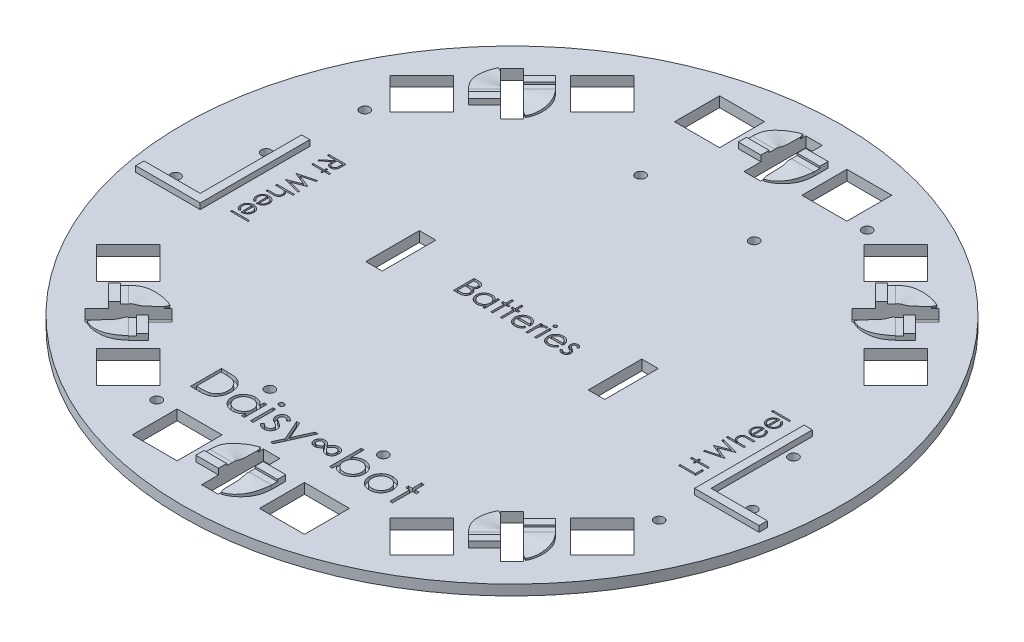
SolidWorks part; units mm, degrees
ref_plane "Front" through (0, 0, 0) normal (0, 0, 1) x (1, 0, 0)
ref_plane "Top" through (0, 0, 0) normal (0, 1, 0) x (1, 0, 0)
ref_plane "Right" through (0, 0, 0) normal (1, 0, 0) x (0, 0, -1)
sketch "Sketch1" plane through (0, 0, 0) normal (0, 1, 0) x (1, 0, 0)
  circle A0 centre (0, 0) radius 101.6
  dimension "D1" = 203.2
extrude "Boss-Extrude1" add sketch "Sketch1" along normal blind 3.175 contours A0
sketch "Sketch2" plane through (0, 3.175, 0) normal (0, 1, 0) x (1, 0, 0)
  line L1 (-2.54, -93.1333) -> (2.54, -93.1333)
  line L2 (-2.54, -93.1333) -> (-2.54, -74.0833)
  line L3 (-2.54, -74.0833) -> (2.54, -74.0833)
  line L4 (2.54, -93.1333) -> (2.54, -74.0833)
  circle A0 centre (0, 0) radius 101.6 construction
  point P4 (0, -74.0833)
  dimension "D1" = 5.08
  dimension "D2" = 19.05
  dimension "D3" = 93.1333
extrude "Cut-Extrude1" cut sketch "Sketch2" against normal up to next and the other way through all contours L1 L4 L3 L2
sketch "Sketch4" plane through (0, 3.175, 0) normal (0, 1, 0) x (1, 0, 0)
  line L0 (0, -83.6083) -> (-2.9434, -74.5495) construction
  line L1 (-2.9434, -74.5495) -> (0, -83.6083) construction
  line L2 (0, -83.6083) -> (-5.5987, -75.9025) construction
  line L3 (0, -83.6083) -> (-7.7059, -78.0097) construction
  line L4 (0, -83.6083) -> (-9.0588, -80.665) construction
  line L5 (0, -83.6083) -> (-9.525, -83.6083) construction
  line L9 (2.54, -74.0833) -> (-2.54, -74.0833) construction
  line L10 (2.54, -74.0833) -> (2.54, -93.1333) construction
  line L11 (-2.54, -74.0833) -> (-2.54, -93.1333) construction
  line L12 (2.54, -93.1333) -> (-2.54, -93.1333) construction
  circle A0 centre (0, -83.6083) radius 9.525 construction
  point P16 (0, -74.0833)
  point P19 (2.54, -83.6083)
  dimension "D1" = 18
  dimension "D2" = 18
  dimension "D3" = 18
  dimension "D4" = 18
  dimension "D5" = 18
ref_plane "Plane1" through (-24.5719, 0, 7.9839) normal (0.9511, 0, -0.309) x (-0.309, 0, -0.9511)
ref_plane "Plane2" through (-39.7581, 0, 28.886) normal (0.809, 0, -0.5878) x (-0.5878, 0, -0.809)
ref_plane "Plane3" through (-39.7581, 0, 54.7224) normal (0.5878, 0, -0.809) x (-0.809, 0, -0.5878)
ref_plane "Plane4" through (-24.5719, 0, 75.6245) normal (0.309, 0, -0.9511) x (-0.9511, 0, -0.309)
ref_plane "Plane5" through (0, 0, 83.6083) normal (0, 0, -1) x (-1, 0, 0)
sketch "Sketch5" plane through (-24.5719, 0, 7.9839) normal (0.9511, 0, -0.309) x (-0.309, 0, -0.9511)
  line L0 (-69.6725, 3.175) -> (-87.7902, 3.175) construction
  line L1 (-71.2966, 3.175) -> (-69.9913, 3.175)
  line L2 (-71.2966, 3.175) -> (-71.2966, 3.683)
  line L3 (-71.2966, 3.683) -> (-69.9913, 3.683)
  line L4 (-69.9913, 3.175) -> (-69.9913, 3.683)
  dimension "D2" = 0.508
sketch "Sketch6" plane through (-39.7581, 0, 28.886) normal (0.809, 0, -0.5878) x (-0.5878, 0, -0.809)
  line L0 (-58.4417, 3.175) -> (-73.8535, 3.175) construction
  line L1 (-63.3193, 3.175) -> (-58.1156, 3.175)
  line L2 (-63.3193, 3.175) -> (-63.3193, 3.775)
  line L3 (-63.3193, 3.775) -> (-58.1156, 3.775)
  line L4 (-58.1156, 3.175) -> (-58.1156, 3.775)
  dimension "D2" = 0.6
sketch "Sketch7" plane through (-39.7581, 0, 54.7224) normal (0.5878, 0, -0.809) x (-0.809, 0, -0.5878)
  line L0 (-41.4902, 3.175) -> (-52.6875, 3.175) construction
  line L1 (-46.0041, 3.175) -> (-39.6188, 3.175)
  line L2 (-46.0041, 3.175) -> (-46.0041, 4.075)
  line L3 (-46.0041, 4.075) -> (-39.6188, 4.075)
  line L4 (-39.6188, 3.175) -> (-39.6188, 4.075)
  dimension "D2" = 0.9
sketch "Sketch10" plane through (-24.5719, 0, 75.6245) normal (0.309, 0, -0.9511) x (-0.9511, 0, -0.309)
  line L0 (-25.8364, 3.175) -> (-16.7776, 3.175) construction
  line L1 (-23.1657, 3.175) -> (-16.3114, 3.175)
  line L2 (-23.1657, 3.175) -> (-23.1657, 4.375)
  line L3 (-23.1657, 4.375) -> (-16.3114, 4.375)
  line L4 (-16.3114, 3.175) -> (-16.3114, 4.375)
  dimension "D3" = 1.2
sketch "Sketch11" plane through (0, 0, 83.6083) normal (0, 0, -1) x (-1, 0, 0)
  line L0 (0, 3.175) -> (9.525, 3.175) construction
  line L1 (2.54, 3.175) -> (9.525, 3.175)
  line L2 (2.54, 3.175) -> (2.54, 4.375)
  line L3 (2.54, 4.375) -> (9.525, 4.375)
  line L4 (9.525, 3.175) -> (9.525, 4.375)
  dimension "D3" = 1.2
loft "Loft1" add profiles "Sketch5", "Sketch6", "Sketch7", "Sketch10", "Sketch11" connector at (-2.54, 3.683, 75.791) connector at (-2.54, 3.775, 80.1123) connector at (-2.54, 4.075, 81.7629) connector at (-2.54, 4.375, 82.783) connector at (-2.54, 4.375, 83.6083)
sketch "Sketch13" plane through (-104.9799, 0, 83.6083) normal (0, 0, -1) x (-1, 0, 0)
  line L6 (-95.4549, 3.175) -> (-102.4399, 3.175)
  line L7 (-95.4549, 3.175) -> (-95.4549, 4.375)
  line L8 (-95.4549, 4.375) -> (-102.4399, 4.375)
  line L9 (-102.4399, 3.175) -> (-102.4399, 4.375)
extrude "Boss-Extrude4" add sketch "Sketch13" against normal blind 1.7907
sketch "Sketch25" plane through (0, 0, 85.399) normal (0, 0, 1) x (1, 0, 0)
  line L0 (-9.525, 4.375) -> (-2.54, 4.375) construction
  line L1 (-9.525, 3.175) -> (-2.54, 3.175)
  line L2 (-9.525, 3.175) -> (-9.525, 4.975)
  line L3 (-9.525, 4.975) -> (-2.54, 4.975)
  line L4 (-2.54, 3.175) -> (-2.54, 4.975)
  dimension "D1" = 0.6
extrude "Boss-Extrude5" add sketch "Sketch25" along normal blind 2.54
sketch "Sketch14" plane through (-2.54, 0, 0) normal (1, 0, 0) x (0, 0, -1)
  line L0 (-83.6083, 3.175) -> (-83.6083, 0) construction
  line L1 (-74.0833, 0) -> (-93.1333, 0) construction
ref_plane "Plane6" through (0, 0, 0) normal (1, 0, 0) x (0, 0, -1)
sketch "Sketch15" plane through (0, 0, 0) normal (1, 0, 0) x (0, 0, -1)
  line L0 (-83.6083, 0) -> (-83.6083, 3.175) construction
pattern_circular "CirPattern1" count 2 over 360 about axis through (0, 0, 83.6083) along (0, 1, 0) of "Loft1", "Boss-Extrude5", "Boss-Extrude4" reverse direction yes
ref_axis "Axis1" through (0, 50, 0) along (0, -1, 0)
pattern_circular "CirPattern5" count 8 over 360 about axis through (0, 50, 0) along (0, -1, 0) skipping 2, 6 of "CirPattern1", "Cut-Extrude1"
sketch "Sketch18" plane through (0, 3.175, 0) normal (0, 1, 0) x (1, 0, 0)
  line L4 (0, -101.6) -> (0, 101.6) construction
  line L5 (0, -1.7463) -> (0, 1.7463) construction
  line L6 (-101.6, 0) -> (101.6, 0) construction
  circle A8 centre (0, 0) radius 101.6 construction
sketch "Sketch19" plane through (0, 3.175, 0) normal (0, 1, 0) x (1, 0, 0)
  line L0 (-32.0765, -77.4396) -> (0, 0) construction
  line L1 (0, -101.6) -> (0, 101.6) construction
  circle A1 centre (-32.0765, -77.4396) radius 1.5
  dimension "D1" = 83.82
  dimension "D4" = 3
  dimension "D5" = 22.5
extrude "Cut-Extrude2" cut sketch "Sketch19" against normal through all
pattern_circular "CirPattern7" count 4 over 360 about axis through (0, 50, 0) along (0, -1, 0) of "Cut-Extrude2"
sketch "Sketch23" plane through (0, 3.175, 0) normal (0, 1, 0) x (1, 0, 0)
  line L9 (-2.54, -87.939) -> (-2.54, -93.1333) construction
  line L10 (-26.5557, -76.6805) -> (-12.7, -76.6805)
  line L11 (-26.5557, -76.6805) -> (-26.5557, -90.5362)
  line L16 (-26.5557, -90.5362) -> (-12.7, -90.5362)
  line L17 (-12.7, -76.6805) -> (-12.7, -90.5362)
  line L19 (2.54, -74.0833) -> (2.54, -79.2776) construction
  line L20 (0, -50) -> (0, 50) construction
  line L21 (12.7, -76.6805) -> (12.7, -90.5362)
  line L22 (26.5557, -90.5362) -> (12.7, -90.5362)
  line L23 (26.5557, -76.6805) -> (26.5557, -90.5362)
  line L24 (26.5557, -76.6805) -> (12.7, -76.6805)
  point P8 (-2.54, -90.5362)
  point P9 (2.54, -76.6805)
  dimension "D2" = 10.16
extrude "Cut-Extrude6" cut sketch "Sketch23" against normal through all
pattern_circular "CirPattern8" count 8 over 360 about axis through (0, 50, 0) along (0, -1, 0) skipping 2, 6 of "Cut-Extrude6"
sketch "Sketch16" plane through (0, 3.175, 0) normal (0, 1, 0) x (1, 0, 0)
  line L0 (2.54, -74.0833) -> (-2.54, -74.0833) construction
  line L1 (-16.4163, -2.4279) -> (16.4163, -2.4279) construction
  line L2 (0, -101.6) -> (0, 101.6) construction
  line L3 (-71.12, 15.3104) -> (-71.12, -15.3104) construction
  line L4 (-101.6, 0) -> (101.6, 0) construction
  line L5 (71.12, 15.3104) -> (71.12, -15.3104) construction
  line L6 (-31.75, -68.58) -> (31.75, -68.58) construction
  circle A1 centre (0, 0) radius 101.6 construction
  text T0 "Daisy∞bot\r\n" font "Century Gothic" height in points 36
  text T1 "Batteries"
  text T2 "Rt Wheel\r\n" font "Century Gothic" height in points 20
  text T3 "Lt Wheel" font "Century Gothic" height in points 20
  point P4 (-71.12, 0)
  point P7 (0, -68.58)
  point P10 (0, -2.4279)
  point P15 (71.12, 0)
  dimension "D1" = 32.8326
  dimension "D2" = 30.6207
  dimension "D3" = 63.5
  dimension "D4" = 71.12
  dimension "D5" = 71.12
  dimension "D6" = 68.58
extrude "Cut-Extrude4" cut sketch "Sketch16" against normal blind 1.27
sketch "Sketch26" plane through (0, 3.175, 0) normal (0, 1, 0) x (1, 0, 0)
  line L0 (-101.6, 0) -> (101.6, 0) construction
  line L1 (-36.83, 8.255) -> (-31.75, 8.255)
  line L2 (-36.83, 8.255) -> (-36.83, -8.255)
  line L3 (-36.83, -8.255) -> (-31.75, -8.255)
  line L4 (-31.75, 8.255) -> (-31.75, -8.255)
  line L5 (0, -101.6) -> (0, 101.6) construction
  point P4 (-36.83, 0)
  dimension "D1" = 16.51
  dimension "D2" = 5.08
  dimension "D3" = 31.75
extrude "Cut-Extrude7" cut sketch "Sketch26" against normal through all
mirror "Mirror1" about plane through (0, 0, 0) normal (1, 0, 0) of "Cut-Extrude7"
sketch "Sketch27" plane through (0, 0, 0) normal (0, -1, 0) x (1, 0, 0)
  line L0 (0, 101.6) -> (0, -101.6) construction
  line L1 (-101.6, 0) -> (101.6, 0) construction
  circle A0 centre (-17.5, -57.15) radius 1.5
  circle A1 centre (-77.4396, -32.0765) radius 1.5 construction
  dimension "D1" = 17.5
  dimension "D2" = 57.15
extrude "Cut-Extrude8" cut sketch "Sketch27" against normal through all both and the other way through all
mirror "Mirror2" about plane through (0, 0, 0) normal (0, 0, 1) of "Cut-Extrude8"
mirror "Mirror3" about plane through (0, 0, 0) normal (1, 0, 0) of "Mirror2"
sketch "Sketch28" plane through (0, 0, 0) normal (0, -1, 0) x (1, 0, 0)
  line L0 (-21.8435, -50.8) -> (21.8435, -50.8) construction
  line L1 (0, 101.6) -> (0, -101.6) construction
  line L2 (-101.6, 0) -> (101.6, 0) construction
  line L3 (-19.568, 50.8) -> (19.568, 50.8) construction
  text T0 "Bk Caster"
  text T1 "Ft Caster"
  point P3 (0, 50.8)
  point P4 (0, -50.8)
  dimension "D1" = 50.8
  dimension "D2" = 50.8
extrude "Cut-Extrude9" cut sketch "Sketch28" against normal blind 1.27
ref_plane "Plane7" through (101.6, 3.175, 0) normal (1, 0, 0) x (0, 0, -1)
sketch "Sketch33" plane through (0, 3.175, 0) normal (0, 1, 0) x (1, 0, 0)
  line L2 (-101.6, 0) -> (101.6, 0) construction
  line L3 (101.6, -1.7462) -> (101.6, 1.7463) construction
  circle A0 centre (88.9, -14.835) radius 1.5
  circle A1 centre (81.28, 5.485) radius 1.5
  point P4 (96.5042, 5.2933)
  point P5 (0, 0)
  dimension "D1" = 3
  dimension "D3" = 7.62
  dimension "D4" = 14.835
  dimension "D2" = 20.32
  dimension "D5" = 12.7
extrude "Cut-Extrude11" cut sketch "Sketch33" against normal through all
sketch "Sketch34" plane through (0, 3.175, 0) normal (0, 1, 0) x (1, 0, 0)
  line L6 (96.0881, -17.375) -> (78.74, -17.375)
  line L7 (78.74, -17.375) -> (78.74, 13.8514)
  line L8 (78.74, 13.8514) -> (76.2, 13.8514)
  line L9 (76.2, 13.8514) -> (76.2, -19.915)
  line L10 (76.2, -19.915) -> (96.0881, -19.915)
  line L11 (96.0881, -19.915) -> (96.0881, -17.375)
  circle A0 centre (88.9, -14.835) radius 1.5 construction
  circle A1 centre (81.28, 5.485) radius 1.5 construction
  dimension "D3" = 2.54
  dimension "D1" = 2.54
  dimension "D2" = 2.54
extrude "Boss-Extrude7" add sketch "Sketch34" along normal through all
mirror "Mirror4" about plane through (0, 0, 0) normal (1, 0, 0) of "Cut-Extrude11", "Boss-Extrude7"
